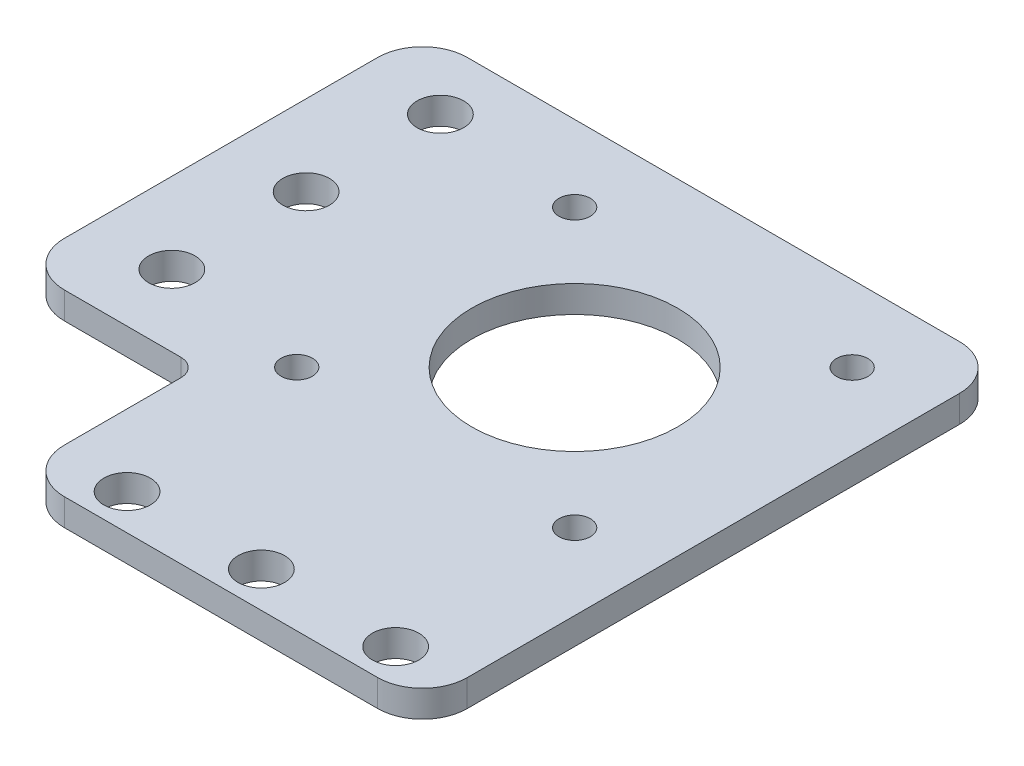
SolidWorks part; units mm, degrees
material "AISI 4340 Steel, annealed"
ref_plane "Front Plane" through (0, 0, 0) normal (0, 0, 1) x (1, 0, 0)
ref_plane "Top Plane" through (0, 0, 0) normal (0, 1, 0) x (1, 0, 0)
ref_plane "Right Plane" through (0, 0, 0) normal (1, 0, 0) x (0, 0, -1)
sketch "Sketch2" plane through (0, 0, 0) normal (0, 1, 0) x (1, 0, 0)
  line L3 (0, 70) -> (65, 70)
  line L5 (65, 70) -> (65, 5)
  line L6 (65, 5) -> (20, 5)
  line L7 (9, 70) -> (9, 25) construction
  line L11 (20, 70) -> (20, 25) construction
  line L12 (20, 25) -> (65, 25) construction
  line L13 (20, 5) -> (20, 25)
  line L14 (20, 25) -> (0, 25)
  line L16 (0, 25) -> (0, 70)
  line L17 (20, 14) -> (65, 14) construction
  circle A5 centre (28, 9) radius 2.6
  circle A6 centre (43, 9) radius 2.6
  circle A7 centre (58, 9) radius 2.6
  circle A17 centre (9, 33) radius 2.6
  circle A18 centre (9, 48) radius 2.6
  circle A19 centre (9, 63) radius 2.6
  line B0 (62, 30.4142) -> (62, 61.5858) construction
  line B1 (61.7071, 62.2929) -> (57.2929, 66.7071) construction
  line B2 (56.5858, 67) -> (25.4142, 67) construction
  line B3 (24.7071, 66.7071) -> (20.2929, 62.2929) construction
  line B4 (20, 61.5858) -> (20, 30.4142) construction
  line B5 (20.2929, 29.7071) -> (24.7071, 25.2929) construction
  line B6 (25.4142, 25) -> (56.5858, 25) construction
  line B7 (57.2929, 25.2929) -> (61.7071, 29.7071) construction
  circle B8 centre (25.5, 61.5) radius 1.75
  circle B9 centre (56.5, 61.5) radius 1.75
  circle B10 centre (56.5, 30.5) radius 1.75
  circle B11 centre (25.4492, 30.5023) radius 1.75
  circle B12 centre (41, 46) radius 11.5
  arc B13 (62, 61.5858) -> (61.7071, 62.2929) centre (61, 61.5858) ccw construction
  arc B14 (57.2929, 66.7071) -> (56.5858, 67) centre (56.5858, 66) ccw construction
  arc B15 (25.4142, 67) -> (24.7071, 66.7071) centre (25.4142, 66) ccw construction
  arc B16 (20.2929, 62.2929) -> (20, 61.5858) centre (21, 61.5858) ccw construction
  arc B17 (20, 30.4142) -> (20.2929, 29.7071) centre (21, 30.4142) ccw construction
  arc B18 (24.7071, 25.2929) -> (25.4142, 25) centre (25.4142, 26) ccw construction
  arc B19 (56.5858, 25) -> (57.2929, 25.2929) centre (56.5858, 26) ccw construction
  arc B20 (61.7071, 29.7071) -> (62, 30.4142) centre (61, 30.4142) ccw construction
  dimension "D9" = 5.2
  dimension "D2" = 15
  dimension "D4" = 8
  dimension "D3" = 15
  dimension "D5" = 20
  dimension "D6" = 15
  dimension "D7" = 15
  dimension "D8" = 8
  dimension "D10" = 9
  dimension "D13" = 9
  dimension "D14" = 65
  dimension "D15" = 65
  dimension "D16" = 20
sketch_block_instance "nema 17 Block1-1"
sketch_block "nema 17 Block1" parameters "D1"=3, "D2"=22
base flange "Base-Flange1" sketch "Sketch2" thickness 3 reverse thickness direction no parameters "D1"=5
fillet "Fillet1" radius 5 5 edges at (65, -1.5, -70) (65, -1.5, -5) (0, -1.5, -70) (0, -1.5, -25) (20, -1.5, -5)
fillet "Fillet2" radius 2 1 edges at (20, -1.5, -25)
sketch "Bend-Lines1" [suppressed] plane through (0, 0, 0) normal (0, 1, 0) x (1, 0, 0)
sketch "Bounding-Box1" [suppressed] plane through (0, 0, 0) normal (0, 1, 0) x (1, 0, 0)
sheet metal parameters "Sheet-Metal3" thickness 3 parameters "D1"=5
flat pattern "Flat-Pattern3" [suppressed]
sketch "Bend-Lines2" plane through (0, 0, 0) normal (0, 1, 0) x (1, 0, 0)
sketch3d "Bounding-Box2" [suppressed]
  line L0 (0, 5, 0) -> (65, 5, 0) construction
  line L1 (0, 70, 0) -> (65, 70, 0) construction
  line L2 (0, 5, 0) -> (0, 70, 0) construction
  line L3 (65, 5, 0) -> (65, 70, 0) construction
